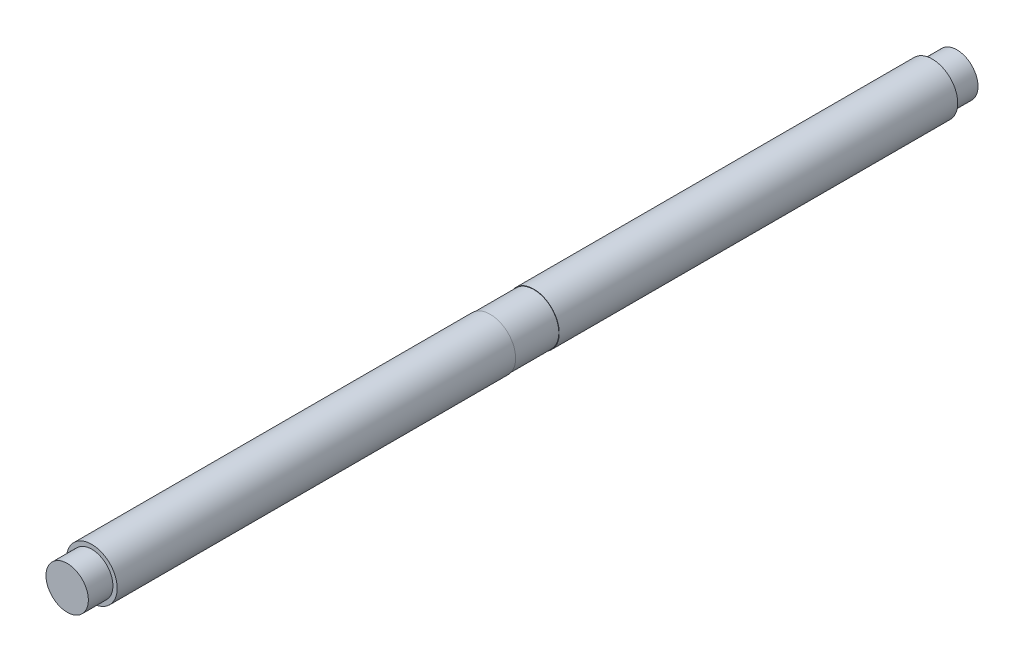
SolidWorks part; units mm, degrees
ref_plane "正面" through (0, 0, 0) normal (0, 0, 1) x (1, 0, 0)
ref_plane "平面" through (0, 0, 0) normal (0, 1, 0) x (1, 0, 0)
ref_plane "右側面" through (0, 0, 0) normal (1, 0, 0) x (0, 0, -1)
sketch "ｽｹｯﾁ1" plane through (0, 0, 0) normal (0, 0, 1) x (1, 0, 0)
  circle A0 centre (0, 0) radius 6
  dimension "D1" = 12
extrude "ﾎﾞｽ - 押し出し1" add sketch "ｽｹｯﾁ1" along normal mid plane 210
sketch "ｽｹｯﾁ2" plane through (0, 0, -105) normal (0, 0, -1) x (-1, 0, 0)
  circle A0 centre (0, 0) radius 6
  circle A1 centre (0, 0) radius 5
  dimension "D1" = 10
extrude "ｶｯﾄ - 押し出し1" cut sketch "ｽｹｯﾁ2" against normal blind 5.8
mirror "ﾐﾗｰ1" about plane through (0, 0, 0) normal (0, 0, 1) of "ｶｯﾄ - 押し出し1"
ref_plane "平面1" through (0, 0, 0) normal (0, 0, 1) x (1, 0, 0)
sketch "ｽｹｯﾁ3" plane through (0, 0, 0) normal (0, 0, 1) x (1, 0, 0)
  circle A0 centre (0, 0) radius 6
  circle A1 centre (0, 0) radius 5.9
  circle A2 centre (0, 0) radius 6 construction
  dimension "D1" = 0.1
extrude "ｶｯﾄ - 押し出し2" cut sketch "ｽｹｯﾁ3" against normal mid plane 10.3
